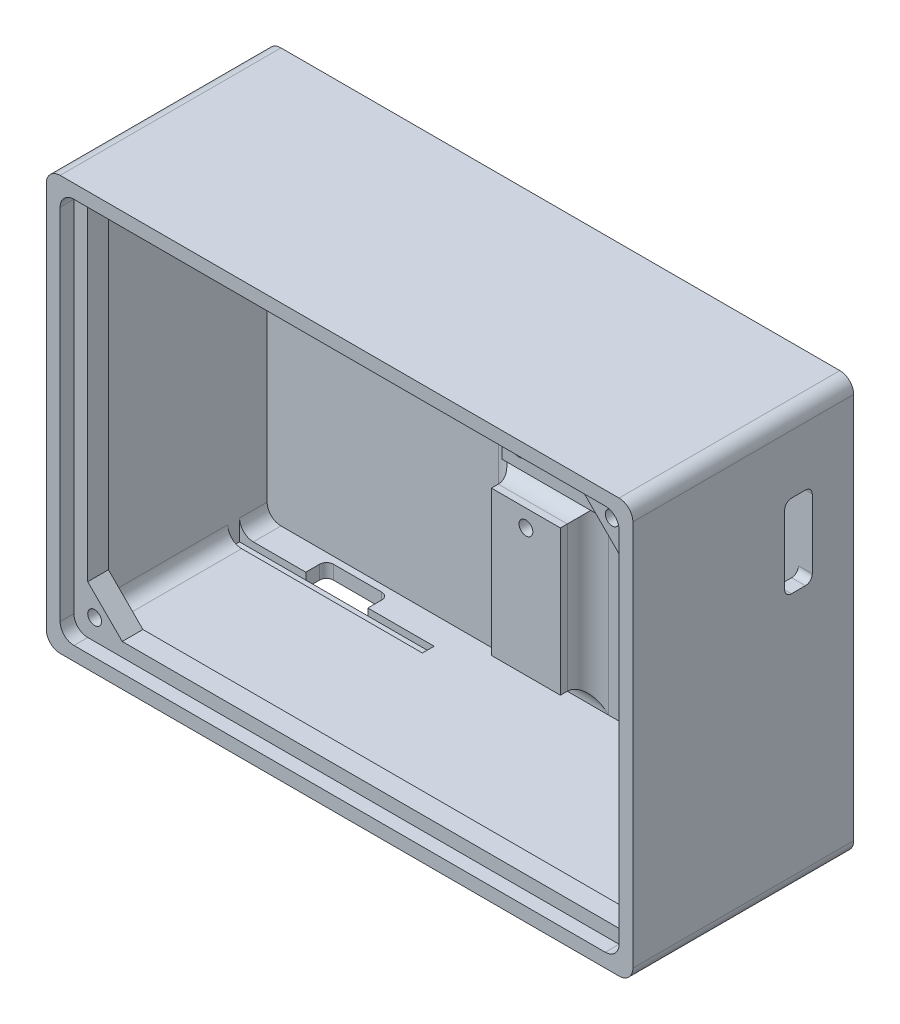
SolidWorks part; units mm, degrees
ref_plane "Front Plane" through (0, 0, 0) normal (0, 0, 1) x (1, 0, 0)
ref_plane "Top Plane" through (0, 0, 0) normal (0, 1, 0) x (1, 0, 0)
ref_plane "Right Plane" through (0, 0, 0) normal (1, 0, 0) x (0, 0, -1)
sketch "Sketch1" plane through (0, 0, 0) normal (0, 0, 1) x (1, 0, 0)
  line L1 (0, 0) -> (85, 0)
  line L2 (0, 0) -> (0, 60)
  line L3 (0, 60) -> (85, 60)
  line L4 (85, 0) -> (85, 60)
  dimension "D1" = 85
  dimension "D2" = 60
extrude "Boss-Extrude1" add sketch "Sketch1" along normal blind 2
sketch "Sketch2" plane through (0, 0, 2) normal (0, 0, 1) x (1, 0, 0)
  line L0 (2, 58) -> (83, 58)
  line L1 (0, 60) -> (85, 60)
  line L2 (0, 60) -> (0, 0)
  line L3 (0, 0) -> (85, 0)
  line L4 (85, 60) -> (85, 0)
  line L5 (83, 58) -> (83, 2)
  line L6 (2, 2) -> (83, 2)
  line L7 (2, 58) -> (2, 2)
  dimension "D1" = 2
extrude "Boss-Extrude2" add sketch "Sketch2" along normal blind 30
sketch "Sketch4" plane through (0, 0, 2) normal (0, 0, 1) x (1, 0, 0)
  line L0 (2, 58) -> (2, 2) construction
  line L1 (2, 56) -> (30, 56) construction
  line L2 (2, 56) -> (2, 1) construction
  line L3 (2, 1) -> (30, 1) construction
  line L4 (30, 56) -> (30, 1) construction
  line L5 (0, 0) -> (85, 0) construction
  line L6 (2, 54) -> (30, 54) construction
  circle A0 centre (4.5, 54) radius 1
  circle A1 centre (28.5, 54) radius 1
  circle A2 centre (4.5, 54) radius 2
  circle A3 centre (28.5, 54) radius 2
  point P10 (4.5, 54)
  point P11 (28.5, 54)
  dimension "D1" = 55
  dimension "D2" = 28
  dimension "D3" = 1
  dimension "D4" = 2
  dimension "D5" = 2.5
  dimension "D6" = 1.5
extrude "Boss-Extrude3" add sketch "Sketch4" along normal blind 4
fillet "Fillet1" radius 5 2 edges at (26.5, 54, 2) (2.5, 54, 2)
sketch "Sketch5" plane through (0, 0, 6) normal (0, 0, 1) x (1, 0, 0)
  line L0 (2, 47.5699) -> (2, 58) construction
  line L1 (2, 52.785) -> (36.1419, 52.785)
  line L2 (2, 52.785) -> (2, 51.2806)
  line L3 (2, 51.2806) -> (36.1419, 51.2806)
  line L4 (36.1419, 52.785) -> (36.1419, 51.2806)
extrude "Cut-Extrude1" cut sketch "Sketch5" against normal blind 1.5
fillet "Fillet2" radius 2 8 edges at (0, 0, 16) (2, 2, 17) (83, 2, 17) (85, 0, 16) (85, 60, 16) (83, 58, 17) (0, 60, 16) (2, 58, 17.2506)
sketch "Sketch6" plane through (0, 0, 0) normal (0, -1, 0) x (1, 0, 0)
  line L1 (30.2, 7.7) -> (2, 7.7)
  line L2 (30.2, 7.7) -> (30.2, 6)
  line L3 (30.2, 6) -> (2, 6)
  line L4 (2, 7.7) -> (2, 6)
  line L5 (0, 0) -> (0, 32) construction
  line L6 (2, 0) -> (83, 0) construction
  dimension "D1" = 28.2
  dimension "D2" = 1.7
  dimension "D3" = 2
  dimension "D4" = 6
extrude "Cut-Extrude2" cut sketch "Sketch6" against normal blind 7.5 from offset 1 offset against normal yes
sketch "Sketch7" plane through (0, 0, 0) normal (0, -1, 0) x (1, 0, 0)
  line L0 (2, 6) -> (30.2, 6) construction
  line L1 (11.6, 6) -> (20.6, 6)
  line L2 (11.6, 6) -> (11.6, 4)
  line L3 (12.6, 3) -> (19.6, 3)
  line L4 (20.6, 6) -> (20.6, 4)
  line L5 (16.1, 7.7) -> (16.1, 0) construction
  line L6 (30.2, 7.7) -> (2, 7.7) construction
  line L7 (2, 0) -> (83, 0) construction
  arc A0 (19.6, 3) -> (20.6, 4) centre (19.6, 4) ccw
  arc A1 (11.6, 4) -> (12.6, 3) centre (12.6, 4) ccw
  point P14 (20.6, 3)
  point P17 (11.6, 3)
  dimension "D4" = 1
  dimension "D1" = 9
  dimension "D2" = 3
  dimension "D3" = 4.5
extrude "Cut-Extrude3" cut sketch "Sketch7" against normal blind 7.5
sketch "Sketch8" plane through (0, 0, 2) normal (0, 0, 1) x (1, 0, 0)
  line L0 (43.5, 26) -> (43.5, 5) construction
  line L1 (37, 26) -> (80, 26) construction
  line L2 (37, 26) -> (37, 5) construction
  line L3 (37, 5) -> (80, 5) construction
  line L4 (80, 26) -> (80, 5) construction
  line L5 (38.5, 26) -> (38.5, 5)
  line L6 (73.5, 26) -> (73.5, 5) construction
  line L7 (68.5, 26) -> (68.5, 5)
  line L8 (48.5, 26) -> (48.5, 5)
  line L9 (78.5, 26) -> (78.5, 5)
  line L10 (38.5, 26) -> (48.5, 26)
  line L11 (68.5, 26) -> (78.5, 26)
  line L12 (38.5, 5) -> (48.5, 5)
  line L13 (68.5, 5) -> (78.5, 5)
  line L14 (83, 4) -> (83, 56) construction
  line L16 (4, 2) -> (81, 2) construction
  circle A0 centre (43.5, 23.5) radius 1
  circle A1 centre (73.5, 7.5) radius 1
  dimension "D7" = 2.5
  dimension "D1" = 43
  dimension "D2" = 21
  dimension "D3" = 6.5
  dimension "D4" = 6.5
  dimension "D8" = 2.5
  dimension "D9" = 30
  dimension "D10" = 3
  dimension "D11" = 3
  dimension "D5" = 5
  dimension "D6" = 5
extrude "Boss-Extrude4" add sketch "Sketch8" along normal blind 4
fillet "Fillet3" radius 3 8 edges at (43.5, 26, 2) (38.5, 15.5, 2) (43.5, 5, 2) (48.5, 15.5, 2) (68.5, 15.5, 2) (73.5, 5, 2) (73.5, 26, 2) (78.5, 15.5, 2)
sketch "Sketch9" plane through (85, 0, 0) normal (1, 0, 0) x (0, 0, -1)
  line L0 (0, 58) -> (-32, 58) construction
  line L1 (-7, 49.5) -> (-9, 49.5)
  line L2 (-6, 48.5) -> (-6, 38.5)
  line L3 (-7, 37.5) -> (-9, 37.5)
  line L4 (-10, 48.5) -> (-10, 38.5)
  line L5 (0, 2) -> (0, 58) construction
  arc A0 (-9, 37.5) -> (-10, 38.5) centre (-9, 38.5) cw
  arc A1 (-6, 38.5) -> (-7, 37.5) centre (-7, 38.5) cw
  arc A2 (-7, 49.5) -> (-6, 48.5) centre (-7, 48.5) cw
  arc A3 (-9, 49.5) -> (-10, 48.5) centre (-9, 48.5) ccw
  point P10 (-10, 37.5)
  point P13 (-6, 37.5)
  point P16 (-6, 49.5)
  dimension "D5" = 1
  dimension "D1" = 12
  dimension "D2" = 4
  dimension "D3" = 8.5
  dimension "D4" = 6
extrude "Cut-Extrude4" cut sketch "Sketch9" against normal blind 4
sketch "Sketch10" plane through (0, 0, 2) normal (0, 0, 1) x (1, 0, 0)
  line L0 (44.5, 52.3971) -> (69.5, 52.3971)
  line L1 (40, 56.8971) -> (74, 56.8971)
  line L2 (40, 56.8971) -> (40, 30.3971)
  line L3 (40, 30.3971) -> (74, 30.3971)
  line L4 (81, 52.3971) -> (83, 52.3971)
  line L5 (69.5, 52.3971) -> (69.5, 34.8971)
  line L6 (44.5, 34.8971) -> (69.5, 34.8971)
  line L7 (44.5, 52.3971) -> (44.5, 34.8971)
  line L9 (83, 4) -> (83, 56) construction
  line L10 (74, 56.8971) -> (74, 30.3971) construction
  line L11 (83, 52.3971) -> (83, 34.8971)
  line L12 (83, 4) -> (83, 56) construction
  line L13 (78.5, 52.3971) -> (78.5, 34.8971) construction
  line L14 (81, 43.6471) -> (40, 43.6471) construction
  line L15 (83, 34.8971) -> (81, 34.8971)
  circle A0 centre (42.5, 54.3971) radius 1
  circle A1 centre (42.5, 32.8971) radius 1
  circle A2 centre (71.5, 54.3971) radius 1
  circle A3 centre (71.5, 32.8971) radius 1
  circle A4 centre (78.5, 50.3971) radius 1
  circle A5 centre (78.5, 36.8971) radius 1
  spline S0 degree 2 poles (74, 56.8971) (76.5952, 53.2372) (81, 52.3971) knots 0 0 0 1 1 1
  spline S1 degree 2 poles (74, 30.3971) (76.5952, 34.0571) (81, 34.8971) knots 0 0 0 1 1 1
  dimension "D7" = 2.5
  dimension "D17" = 2
  dimension "D1" = 34
  dimension "D2" = 26.5
  dimension "D4" = 2.5
  dimension "D5" = 2.5
  dimension "D6" = 2.5
  dimension "D8" = 2.5
  dimension "D9" = 2.5
  dimension "D10" = 2.5
  dimension "D11" = 2.5
  dimension "D12" = 2.5
  dimension "D13" = 2.5
  dimension "D15" = 29
  dimension "D16" = 21.5
  dimension "D18" = 2
  dimension "D3" = 4.5
extrude "Boss-Extrude5" add sketch "Sketch10" along normal blind 4
sketch "Sketch11" plane through (0, 0, 32) normal (0, 0, 1) x (1, 0, 0)
  line L0 (4, 56) -> (76, 56)
  line L1 (2, 58) -> (83, 58)
  line L2 (2, 58) -> (2, 2)
  line L3 (2, 2) -> (83, 2)
  line L4 (83, 58) -> (83, 2)
  line L5 (81, 51) -> (81, 4)
  line L6 (9, 4) -> (81, 4)
  line L7 (4, 56) -> (4, 9)
  line L8 (76, 56) -> (81, 51)
  line L9 (4, 9) -> (9, 4)
  line L11 (4, 56) -> (4, 4) construction
  line L12 (4, 4) -> (81, 4) construction
  line L13 (81, 56) -> (81, 4) construction
  line L14 (4, 56) -> (81, 56) construction
  dimension "D1" = 2
extrude "Boss-Extrude6" add sketch "Sketch11" against normal blind 3 from offset 2 offset against normal yes
fillet "Fillet4" radius 2 8 edges at (82.4142, 57.4142, 27) (83, 30, 27) (82.4142, 2.5858, 27) (42.5, 2, 27) (2.5858, 2.5858, 27) (2, 30, 27) (2.5858, 57.4142, 27) (42.5, 58, 27)
sketch "Sketch12" plane through (0, 0, 30) normal (0, 0, 1) x (1, 0, 0)
  line L0 (2, 56) -> (2, 4) construction
  line L1 (4, 2) -> (81, 2) construction
  line L2 (83, 4) -> (83, 56) construction
  line L3 (81, 58) -> (4, 58) construction
  circle A0 centre (5, 5) radius 1
  circle A1 centre (80, 55) radius 1
  dimension "D1" = 3
  dimension "D2" = 3
  dimension "D3" = 3
  dimension "D4" = 3
extrude "Cut-Extrude5" cut sketch "Sketch12" against normal blind 5
sketch "Sketch13" plane through (0, 0, 6) normal (0, 0, 1) x (1, 0, 0)
  line L0 (44.5, 34.8971) -> (69.5, 34.8971) construction
  line L1 (60, 34.8971) -> (68, 34.8971)
  line L2 (60, 34.8971) -> (60, 30.3971)
  line L3 (60, 30.3971) -> (68, 30.3971)
  line L4 (68, 34.8971) -> (68, 30.3971)
  line L5 (40, 30.3971) -> (74, 30.3971) construction
  line L6 (40, 56.8971) -> (40, 30.3971) construction
  dimension "D1" = 20
  dimension "D2" = 8
extrude "Cut-Extrude6" cut sketch "Sketch13" against normal blind 3
fillet "Fillet5" radius 1 4 edges at (60, 32.6471, 6) (68, 32.6471, 6) (68, 32.6471, 3) (60, 32.6471, 3)
